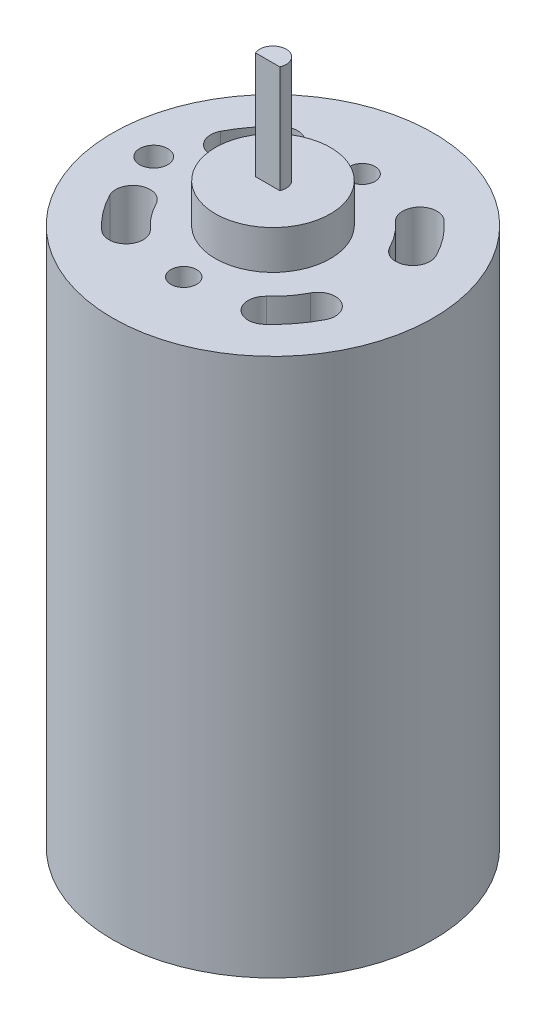
SolidWorks part; units mm, degrees
ref_plane "Front Plane" through (0, 0, 0) normal (0, 0, 1) x (1, 0, 0)
ref_plane "Top Plane" through (0, 0, 0) normal (0, 1, 0) x (1, 0, 0)
ref_plane "Right Plane" through (0, 0, 0) normal (1, 0, 0) x (0, 0, -1)
sketch "Sketch1" plane through (0, 0, 0) normal (0, 1, 0) x (1, 0, 0)
  circle A0 centre (0, 0) radius 13.843
  dimension "D1" = 27.686
extrude "Boss-Extrude1" add sketch "Sketch1" along normal blind 46.482 contours A0
sketch "Sketch2" plane through (0, 46.482, 0) normal (0, 1, 0) x (1, 0, 0)
  circle A0 centre (0, 0) radius 4.9657
  dimension "D1" = 9.9314
extrude "Boss-Extrude2" add sketch "Sketch2" along normal blind 3.3528
sketch "Sketch3" plane through (0, 0, 0) normal (0, -1, 0) x (1, 0, 0)
  circle A0 centre (0, 0) radius 4.953
  dimension "D1" = 9.906
extrude "Boss-Extrude3" add sketch "Sketch3" along normal blind 2.8956
sketch "Sketch4" plane through (0, 49.8348, 0) normal (0, 1, 0) x (1, 0, 0)
  line L0 (-1.0476, -0.4572) -> (1.0476, -0.4572)
  line L1 (0, 1.143) -> (0, -0.4572) construction
  arc A0 (1.0476, -0.4572) -> (-1.0476, -0.4572) centre (0, 0) ccw
  dimension "D1" = 2.286
  dimension "D2" = 1.6002
extrude "Boss-Extrude4" add sketch "Sketch4" along normal blind 9.2583
sketch "Sketch5" plane through (0, 46.482, 0) normal (0, 1, 0) x (1, 0, 0)
  line L0 (0, 13.843) -> (0, 8.8138) construction
  line L1 (0, -8.8138) -> (0, -13.843) construction
  line L2 (-13.843, 0) -> (-11.5062, 0) construction
  line L3 (-7.9903, -2.6099) -> (-7.9903, 2.6099) construction
  line L4 (-6.0137, 8.1534) -> (-6.0137, -8.1534) construction
  circle A0 centre (0, 7.7026) radius 1.1112
  circle A1 centre (0, -7.7026) radius 1.1112
  circle A2 centre (-10.2934, 0) radius 1.2128
  circle A3 centre (0, 0) radius 13.843 construction
  arc A4 (-5.0185, 5.5641) -> (-6.668, 3.418) centre (0, 0) ccw
  arc A5 (-7.0089, 7.7709) -> (-9.3126, 4.7735) centre (0, 0) ccw
  arc A6 (-9.3126, 4.7735) -> (-6.668, 3.418) centre (-7.9903, 4.0958) ccw
  arc A7 (-5.0185, 5.5641) -> (-7.0089, 7.7709) centre (-6.0137, 6.6675) ccw
  arc A8 (-6.668, -3.418) -> (-9.3126, -4.7735) centre (-7.9903, -4.0958) ccw
  arc A9 (-7.0089, -7.7709) -> (-5.0185, -5.5641) centre (-6.0137, -6.6675) ccw
  arc A10 (-6.668, -3.418) -> (-5.0185, -5.5641) centre (0, 0) ccw
  arc A11 (-9.3126, -4.7735) -> (-7.0089, -7.7709) centre (0, 0) ccw
  point P28 (-7.9903, 0)
  point P31 (-5.7894, 6.9046)
  dimension "D1" = 2.2225
  dimension "D3" = 2.4257
  dimension "D5" = 14.986
  dimension "D6" = 20.9296
  dimension "D2" = 5.0292
  dimension "D4" = 2.3368
  dimension "D7" = 5.2197
  dimension "D8" = 16.3068
extrude "Cut-Extrude1" cut sketch "Sketch5" against normal blind 5.4356
mirror "Mirror1" about plane through (0, 0, 0) normal (1, 0, 0) of face at (-8.229, 43.7642, -6.3247) of face at (-5.462, 43.7642, -7.1651) of face at (-5.8921, 43.7642, -4.5286) of face at (-8.3292, 43.7642, -3.4346) of face at (-5.8921, 43.7642, 4.5286) of face at (-5.462, 43.7642, 7.1651) of face at (-8.229, 43.7642, 6.3247) of face at (-8.3292, 43.7642, 3.4346) of face at (-6.9542, 41.0464, 5.3448) of face at (-6.9542, 41.0464, -5.3448)
